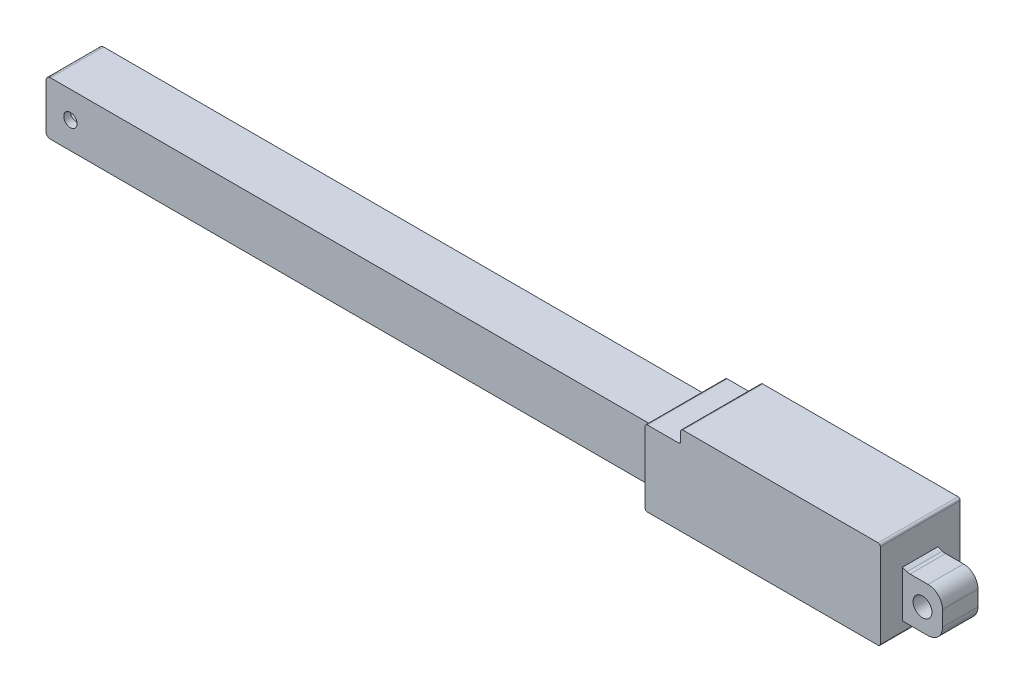
SolidWorks part; units mm, degrees
ref_plane "Front Plane" through (0, 0, 0) normal (0, 0, 1) x (1, 0, 0)
ref_plane "Top Plane" through (0, 0, 0) normal (0, 1, 0) x (1, 0, 0)
ref_plane "Right Plane" through (0, 0, 0) normal (1, 0, 0) x (0, 0, -1)
sketch "Sketch2" plane through (0, 0, 0) normal (0, 0, 1) x (1, 0, 0)
  line L0 (138, 12) -> (138, 14)
  line L1 (1, 0) -> (138, 0)
  line L2 (0, 1) -> (0, 11)
  line L3 (1, 12) -> (138, 12)
  line L4 (138, 0) -> (138, 12)
  line L5 (138, 0) -> (138, -2)
  line L6 (138.5, -2.5) -> (190.5, -2.5)
  line L7 (191, 0) -> (191, -2)
  line L8 (190.5, 17.5) -> (146.5, 17.5)
  line L9 (146, 17) -> (146, 15)
  line L10 (145.5, 14.5) -> (138.5, 14.5)
  line L11 (191, 0) -> (196.7317, 0)
  line L12 (200, 3.2683) -> (200, 6.7317)
  line L13 (196.7317, 10) -> (192.6999, 10)
  line L14 (192, 10.1265) -> (191, 10.5)
  line L15 (195.5, 0) -> (195.5, 10) construction
  line L16 (2, 12) -> (2, 0)
  line L17 (191, 10.5) -> (191, 17)
  line L18 (2, 6) -> (4, 6) construction
  line L19 (0, 6) -> (2, 6) construction
  arc A0 (0, 11) -> (1, 12) centre (1, 11) cw
  arc A1 (1, 0) -> (0, 1) centre (1, 1) cw
  arc A2 (146.5, 17.5) -> (146, 17) centre (146.5, 17) ccw
  arc A3 (191, 17) -> (190.5, 17.5) centre (190.5, 17) ccw
  arc A4 (190.5, -2.5) -> (191, -2) centre (190.5, -2) ccw
  arc A5 (138, -2) -> (138.5, -2.5) centre (138.5, -2) ccw
  arc A6 (138, 14) -> (138.5, 14.5) centre (138.5, 14) cw
  arc A7 (146, 15) -> (145.5, 14.5) centre (145.5, 15) cw
  arc A8 (196.7317, 0) -> (200, 3.2683) centre (196.7317, 3.2683) ccw
  arc A9 (200, 6.7317) -> (196.7317, 10) centre (196.7317, 6.7317) ccw
  circle A10 centre (195.5, 5) radius 2.125
  arc A11 (192.6999, 10) -> (192, 10.1265) centre (192.6999, 12) cw
  circle A12 centre (5.5, 6) radius 1.5
  point P7 (0, 12)
  point P10 (0, 0)
  point P23 (191, -2.5)
  point P26 (138, -2.5)
  point P29 (138, 14.5)
  point P32 (146, 14.5)
  point P44 (195.5, 5)
  point P54 (4, 6)
  dimension "D3" = 1
  dimension "D8" = 0.5
  dimension "D12" = 4.25
  dimension "D13" = 2
  dimension "D14" = 3
  dimension "D1" = 138
  dimension "D2" = 12
  dimension "D4" = 53
  dimension "D5" = 17
  dimension "D6" = 20
  dimension "D7" = 8
  dimension "D9" = 9
  dimension "D10" = 10
  dimension "D11" = 4.5
  dimension "D15" = 2
  dimension "D16" = 1
  dimension "D17" = 0.5
extrude "Boss-Extrude1" add sketch "Sketch2" along normal mid plane 18 contours L9 A7 L10 A6 L0 L4 L5 A5 L6 A4 A3 L8 A2 region at (166.9744, 7.1558, 0)
extrude "Boss-Extrude2" add sketch "Sketch2<3>" along normal mid plane 12 contours L3 L16 L1 L4 A12 region at (70.2806, 6, 0)
sketch "Sketch2<3>" plane through (0, 0, 0) normal (0, 0, 1) x (1, 0, 0) same geometry as "Sketch2"
extrude "Boss-Extrude3" add sketch "Sketch2<4>" along normal mid plane 12 contours A1 L1 L16 L3 A0 L2 region at (1.0141, 6, 0)
sketch "Sketch2<4>" plane through (0, 0, 0) normal (0, 0, 1) x (1, 0, 0) same geometry as "Sketch2"
extrude "Boss-Extrude4" add sketch "Sketch2<5>" along normal mid plane 9 contours L13 A11 L14 L11 A8 L12 A9 A10 region at (166.9744, 7.1558, 0)
sketch "Sketch2<5>" plane through (0, 0, 0) normal (0, 0, 1) x (1, 0, 0) same geometry as "Sketch2"
sketch "Sketch3" plane through (0, 0, 0) normal (-1, 0, 0) x (0, 0, 1)
  line L0 (-6, 1) -> (-4.5, 1)
  line L1 (6, 1) -> (-6, 1) construction
  line L2 (-4.5, 1) -> (-4.5, 1.5)
  line L4 (-4.5, 1.5) -> (4.5, 1.5)
  line L5 (-4.5, 1.5) -> (-4.5, 10.5)
  line L6 (-4.5, 10.5) -> (4.5, 10.5)
  line L7 (4.5, 1.5) -> (4.5, 10.5)
  dimension "D1" = 1.5
  dimension "D2" = 9
  dimension "D3" = 9
  dimension "D4" = 0.5
sketch "Sketch7" plane through (0, 0, 0) normal (-1, 0, 0) x (0, 0, 1)
  line L0 (0, 1) -> (6, 6) construction
  line L1 (6, 1) -> (-6, 1) construction
  line L2 (6, 1) -> (6, 11) construction
  line L3 (6, 6) -> (0, 6) construction
  circle A0 centre (0, 6) radius 4.5
  dimension "D1" = 9
extrude "Cut-Extrude4" cut sketch "Sketch7" against normal blind 138
sketch "Sketch8" plane through (0, 0, 9) normal (0, 0, 1) x (1, 0, 0)
  line L0 (191, 10.5) -> (211.4521, 15.9059)
  line L1 (211.4521, 15.9059) -> (206.5707, -3.8477)
  line L2 (206.5707, -3.8477) -> (191, 0)
  line L3 (191, 0) -> (196.7317, 0) construction
  line L4 (191, 0) -> (191, 10.5)
extrude "Cut-Extrude6" cut sketch "Sketch8" against normal mid plane 10
sketch "Sketch10" plane through (0, 0, -9) normal (0, 0, -1) x (-1, 0, 0)
  line L0 (-191, 10.5) -> (-205.2356, 19.9066)
  line L1 (-205.2356, 19.9066) -> (-199.172, -6.3636)
  line L2 (-199.172, -6.3636) -> (-191, 0)
  line L3 (-191, 0) -> (-191, 10.5)
extrude "Cut-Extrude7" cut sketch "Sketch10" against normal mid plane 10
